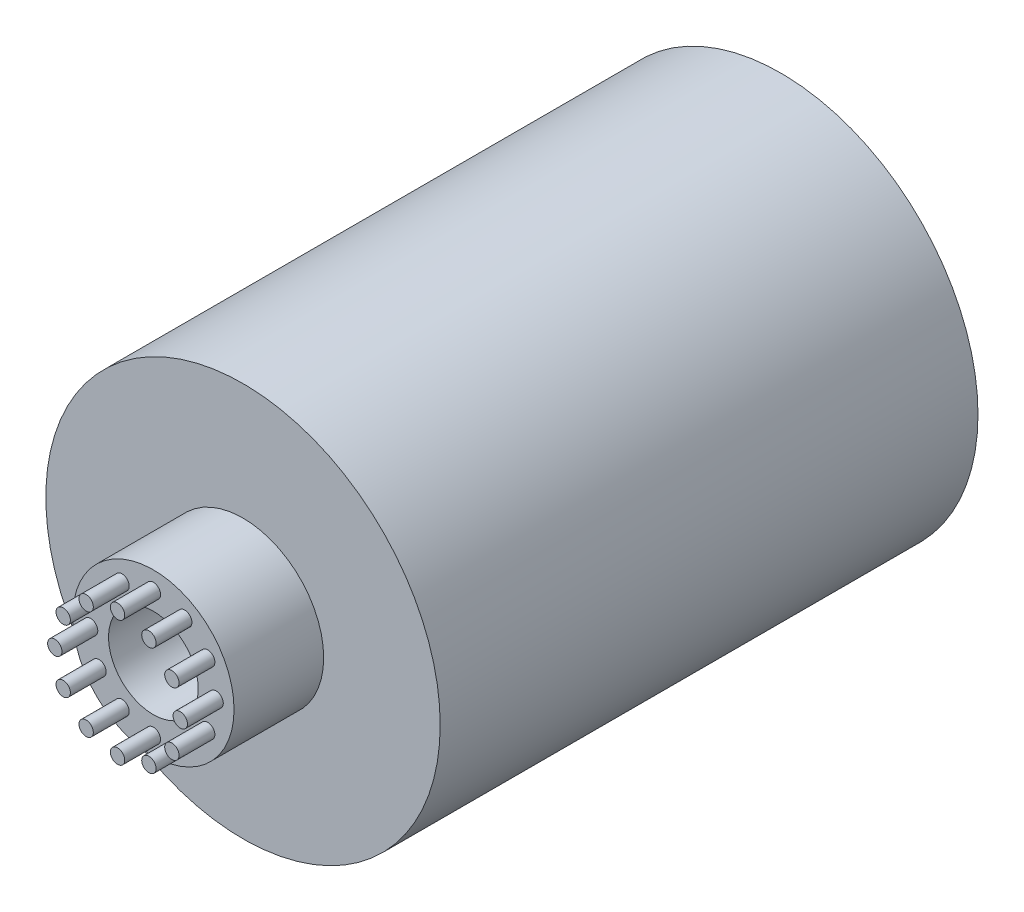
SolidWorks part; units mm, degrees
material "PET"
ref_plane "Front Plane" through (0, 0, 0) normal (0, 0, 1) x (1, 0, 0)
ref_plane "Top Plane" through (0, 0, 0) normal (0, 1, 0) x (1, 0, 0)
ref_plane "Right Plane" through (0, 0, 0) normal (1, 0, 0) x (0, 0, -1)
sketch "Sketch2" plane through (0, 0, 0) normal (0, 0, 1) x (1, 0, 0)
  circle A0 centre (0, 0) radius 11
  dimension "D1" = 22
extrude "Boss-Extrude1" add sketch "Sketch2" along normal blind 30
sketch "Sketch3" plane through (0, 0, 30) normal (0, 0, 1) x (1, 0, 0)
  circle A0 centre (0, 0) radius 4.5
  dimension "D1" = 9
extrude "Boss-Extrude2" add sketch "Sketch3" along normal blind 5
sketch "Sketch4" plane through (0, 0, 0) normal (0, 0, -1) x (-1, 0, 0)
  circle A0 centre (0, 0) radius 4.5
  dimension "D1" = 9
extrude "Boss-Extrude3" add sketch "Sketch4" along normal blind 4
sketch "Sketch5" plane through (0, 0, 35) normal (0, 0, 1) x (1, 0, 0)
  circle A0 centre (0, 0) radius 2.5
  dimension "D1" = 5
extrude "Cut-Extrude1" cut sketch "Sketch5" against normal through all
sketch "Sketch6" plane through (0, 0, 35) normal (0, 0, 1) x (1, 0, 0)
  circle A0 centre (0, 3.5) radius 0.4
  dimension "D1" = 0.8
  dimension "D2" = 3.5
extrude "Boss-Extrude4" add sketch "Sketch6" along normal blind 2
pattern_circular "CirPattern1" count 12 over 360 about axis through (0, 0, 35) along (0, 0, 1) of "Boss-Extrude4"
